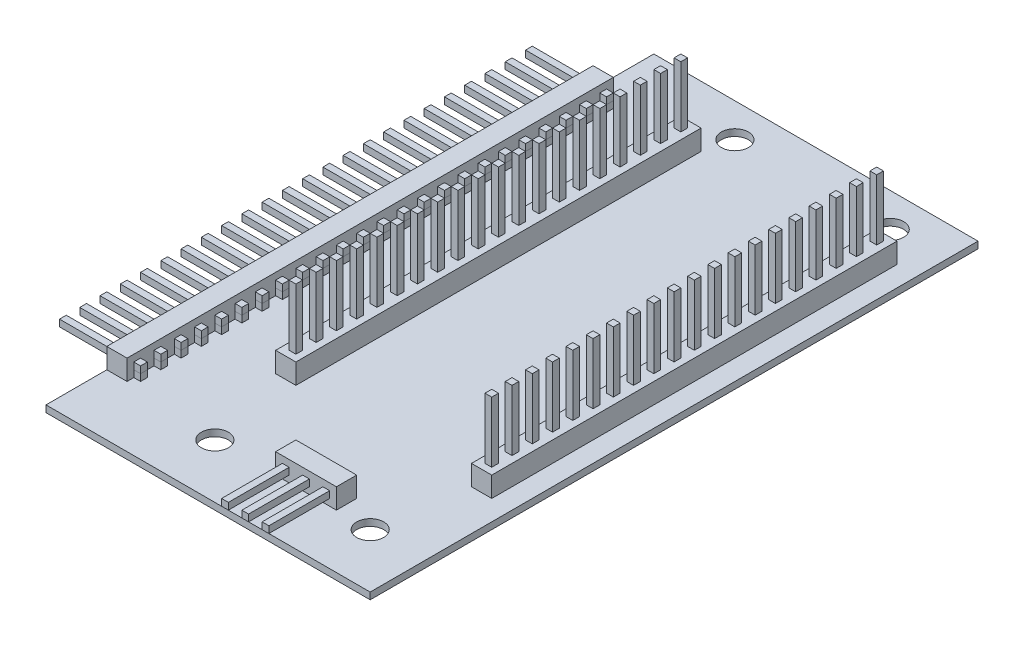
SolidWorks part; units mm, degrees
ref_plane "Front Plane" through (0, 0, 0) normal (0, 0, 1) x (1, 0, 0)
ref_plane "Top Plane" through (0, 0, 0) normal (0, 1, 0) x (1, 0, 0)
ref_plane "Right Plane" through (0, 0, 0) normal (1, 0, 0) x (0, 0, -1)
sketch "Sketch1" plane through (0, 0, 0) normal (0, 1, 0) x (1, 0, 0)
  line L1 (-19.05, 35.7188) -> (19.05, 35.7188)
  line L2 (-19.05, 35.7188) -> (-19.05, -35.7187)
  line L3 (-19.05, -35.7187) -> (19.05, -35.7187)
  line L4 (19.05, 35.7188) -> (19.05, -35.7187)
  line L5 (-19.05, 35.7188) -> (19.05, -35.7187) construction
  line L6 (-19.05, -35.7187) -> (19.05, 35.7188) construction
  point P0 (0, 0)
  dimension "D1" = 38.1
  dimension "D2" = 71.4375
extrude "Boss-Extrude1" add sketch "Sketch1" along normal blind 0.7937
sketch "Sketch2" plane through (0, 0.7937, 0) normal (0, 1, 0) x (1, 0, 0)
  line L0 (0, 0) -> (-19.05, 0) construction
  line L1 (-19.05, 35.7188) -> (-19.05, -35.7187) construction
  line L2 (-19.05, 4.7625) -> (-25.5985, 4.7625) construction
  line L3 (-15.875, 0.7937) -> (-25.4, 0.7937)
  line L4 (-15.875, 0.7937) -> (-15.875, 1.5875)
  line L5 (-15.875, 1.5875) -> (-25.4, 1.5875)
  line L6 (-25.4, 0.7937) -> (-25.4, 1.5875)
  line L7 (-25.4, 3.175) -> (-15.875, 3.175)
  line L8 (-25.4, 3.175) -> (-25.4, 3.9687)
  line L9 (-25.4, 3.9687) -> (-15.875, 3.9687)
  line L10 (-15.875, 3.175) -> (-15.875, 3.9687)
  line L11 (-15.875, 7.9375) -> (-25.4, 7.9375)
  line L12 (-25.4, 8.7312) -> (-25.4, 7.9375)
  line L13 (-15.875, 8.7312) -> (-25.4, 8.7312)
  line L14 (-15.875, 8.7312) -> (-15.875, 7.9375)
  line L15 (-25.4, 5.5562) -> (-15.875, 5.5562)
  line L16 (-15.875, 6.35) -> (-15.875, 5.5562)
  line L17 (-25.4, 6.35) -> (-15.875, 6.35)
  line L18 (-25.4, 6.35) -> (-25.4, 5.5562)
  line L19 (-19.05, 9.525) -> (-25.9028, 9.525) construction
  line L20 (-15.875, 10.3187) -> (-15.875, 11.1125)
  line L21 (-15.875, 10.3187) -> (-25.4, 10.3187)
  line L22 (-25.4, 10.3187) -> (-25.4, 11.1125)
  line L23 (-15.875, 11.1125) -> (-25.4, 11.1125)
  line L24 (-25.4, 12.7) -> (-25.4, 13.4937)
  line L25 (-25.4, 12.7) -> (-15.875, 12.7)
  line L26 (-15.875, 12.7) -> (-15.875, 13.4937)
  line L27 (-25.4, 13.4937) -> (-15.875, 13.4937)
  line L28 (-25.4, 15.0812) -> (-15.875, 15.0812)
  line L29 (-15.875, 15.875) -> (-15.875, 15.0812)
  line L30 (-25.4, 15.875) -> (-15.875, 15.875)
  line L31 (-25.4, 15.875) -> (-25.4, 15.0812)
  line L32 (-15.875, 17.4625) -> (-25.4, 17.4625)
  line L33 (-25.4, 18.2562) -> (-25.4, 17.4625)
  line L34 (-15.875, 18.2562) -> (-25.4, 18.2562)
  line L35 (-15.875, 18.2562) -> (-15.875, 17.4625)
  line L36 (-19.05, 19.05) -> (-25.9028, 19.05) construction
  line L37 (-15.875, 19.8437) -> (-15.875, 20.6375)
  line L38 (-15.875, 19.8437) -> (-25.4, 19.8437)
  line L39 (-25.4, 19.8437) -> (-25.4, 20.6375)
  line L40 (-15.875, 20.6375) -> (-25.4, 20.6375)
  line L41 (-25.4, 22.225) -> (-25.4, 23.0187)
  line L42 (-25.4, 22.225) -> (-15.875, 22.225)
  line L43 (-15.875, 22.225) -> (-15.875, 23.0187)
  line L44 (-25.4, 23.0187) -> (-15.875, 23.0187)
  line L45 (-25.4, 25.4) -> (-15.875, 25.4)
  line L46 (-15.875, 25.4) -> (-15.875, 24.6062)
  line L47 (-25.4, 24.6062) -> (-15.875, 24.6062)
  line L48 (-25.4, 25.4) -> (-25.4, 24.6062)
  line L49 (-15.875, 27.7812) -> (-25.4, 27.7812)
  line L50 (-25.4, 27.7812) -> (-25.4, 26.9875)
  line L51 (-15.875, 26.9875) -> (-25.4, 26.9875)
  line L52 (-15.875, 27.7812) -> (-15.875, 26.9875)
  line L53 (-19.05, -19.05) -> (-25.9028, -19.05) construction
  line L54 (-19.05, -9.525) -> (-25.9028, -9.525) construction
  line L55 (-19.05, -4.7625) -> (-25.5985, -4.7625) construction
  line L56 (-15.875, -27.7812) -> (-15.875, -26.9875)
  line L57 (-15.875, -26.9875) -> (-25.4, -26.9875)
  line L58 (-25.4, -27.7812) -> (-25.4, -26.9875)
  line L59 (-15.875, -27.7812) -> (-25.4, -27.7812)
  line L60 (-25.4, -25.4) -> (-25.4, -24.6062)
  line L61 (-25.4, -24.6062) -> (-15.875, -24.6062)
  line L62 (-15.875, -25.4) -> (-15.875, -24.6062)
  line L63 (-25.4, -25.4) -> (-15.875, -25.4)
  line L64 (-25.4, -23.0187) -> (-15.875, -23.0187)
  line L65 (-15.875, -22.225) -> (-15.875, -23.0187)
  line L66 (-25.4, -22.225) -> (-15.875, -22.225)
  line L67 (-25.4, -22.225) -> (-25.4, -23.0187)
  line L68 (-15.875, -20.6375) -> (-25.4, -20.6375)
  line L69 (-25.4, -19.8437) -> (-25.4, -20.6375)
  line L70 (-15.875, -19.8437) -> (-25.4, -19.8437)
  line L71 (-15.875, -19.8437) -> (-15.875, -20.6375)
  line L72 (-15.875, -18.2562) -> (-15.875, -17.4625)
  line L73 (-15.875, -18.2562) -> (-25.4, -18.2562)
  line L74 (-25.4, -18.2562) -> (-25.4, -17.4625)
  line L75 (-15.875, -17.4625) -> (-25.4, -17.4625)
  line L76 (-25.4, -15.875) -> (-25.4, -15.0812)
  line L77 (-25.4, -15.875) -> (-15.875, -15.875)
  line L78 (-15.875, -15.875) -> (-15.875, -15.0812)
  line L79 (-25.4, -15.0812) -> (-15.875, -15.0812)
  line L80 (-25.4, -13.4937) -> (-15.875, -13.4937)
  line L81 (-15.875, -12.7) -> (-15.875, -13.4937)
  line L82 (-25.4, -12.7) -> (-15.875, -12.7)
  line L83 (-25.4, -12.7) -> (-25.4, -13.4937)
  line L84 (-15.875, -11.1125) -> (-25.4, -11.1125)
  line L85 (-25.4, -10.3187) -> (-25.4, -11.1125)
  line L86 (-15.875, -10.3187) -> (-25.4, -10.3187)
  line L87 (-15.875, -10.3187) -> (-15.875, -11.1125)
  line L88 (-25.4, -6.35) -> (-25.4, -5.5562)
  line L89 (-25.4, -6.35) -> (-15.875, -6.35)
  line L90 (-15.875, -6.35) -> (-15.875, -5.5562)
  line L91 (-25.4, -5.5562) -> (-15.875, -5.5562)
  line L92 (-15.875, -8.7312) -> (-15.875, -7.9375)
  line L93 (-15.875, -8.7312) -> (-25.4, -8.7312)
  line L94 (-25.4, -8.7312) -> (-25.4, -7.9375)
  line L95 (-15.875, -7.9375) -> (-25.4, -7.9375)
  line L96 (-15.875, -3.175) -> (-15.875, -3.9687)
  line L97 (-25.4, -3.9687) -> (-15.875, -3.9687)
  line L98 (-25.4, -3.175) -> (-25.4, -3.9687)
  line L99 (-25.4, -3.175) -> (-15.875, -3.175)
  line L100 (-25.4, -0.7937) -> (-25.4, -1.5875)
  line L101 (-15.875, -1.5875) -> (-25.4, -1.5875)
  line L102 (-15.875, -0.7937) -> (-15.875, -1.5875)
  line L103 (-15.875, -0.7937) -> (-25.4, -0.7937)
  line L104 (-16.6688, 27.7812) -> (-16.6688, 26.9875)
  line L105 (-16.6688, -26.9875) -> (-16.6688, -27.7813)
  line L106 (-16.6688, -24.6062) -> (-16.6688, -25.4)
  line L107 (-16.6688, -22.225) -> (-16.6688, -23.0187)
  line L108 (-16.6688, -17.4625) -> (-16.6688, -20.6375)
  line L109 (-16.6688, -15.0812) -> (-16.6688, -15.875)
  line L110 (-16.6688, -12.7) -> (-16.6688, -13.4937)
  line L111 (-16.6688, -10.3187) -> (-16.6688, -11.1125)
  line L112 (-16.6688, -7.9375) -> (-16.6688, -8.7312)
  line L113 (-16.6688, -5.5562) -> (-16.6688, -6.35)
  line L114 (-16.6688, -3.175) -> (-16.6688, -3.9687)
  line L115 (-16.6688, -0.7937) -> (-16.6688, -1.5875)
  line L116 (-16.6688, 11.1125) -> (-16.6688, 10.3187)
  line L117 (-16.6688, 8.7312) -> (-16.6688, 7.9375)
  line L118 (-16.6688, 6.35) -> (-16.6688, 5.5562)
  line L119 (-16.6688, 3.9687) -> (-16.6688, 3.175)
  line L120 (-16.6688, 1.5875) -> (-16.6688, 0.7938)
  line L121 (-16.6688, 13.4937) -> (-16.6688, 12.7)
  line L122 (-16.6688, 15.875) -> (-16.6688, 15.0812)
  line L123 (-16.6688, 18.2562) -> (-16.6688, 17.4625)
  line L124 (-16.6688, 20.6375) -> (-16.6688, 19.8437)
  line L125 (-16.6688, 23.0187) -> (-16.6688, 22.225)
  line L126 (-16.6688, 25.4) -> (-16.6688, 24.6062)
  point P9 (-25.4, 1.1906)
  dimension "D1" = 3.175
  dimension "D2" = 6.35
  dimension "D3" = 0.7937
  dimension "D4" = 0.7937
  dimension "D5" = 1.5875
  dimension "D6" = 0.7937
  dimension "D7" = 0.7937
  dimension "D8" = 0.7937
  dimension "D9" = 0.7937
extrude "Boss-Extrude2" add sketch "Sketch2" along normal blind 0.7937 separate body contours L49 L104 L51 L52 | L45 L126 L47 L46 | L44 L125 L42 L43 | L40 L124 L38 L37 | L34 L123 L32 L35 | L30 L122 L28 L29 | L27 L121 L25 L26 | L23 L116 L21 L20 | L13 L117 L11 L14 | L17 L118 L15 L16 | L9 L119 L7 L10 | L5 L120 L3 L4 | L103 L115 L101 L102 | L99 L114 L97 L96 | L91 L113 L89 L90 | L95 L112 L93 L92 | L86 L111 L84 L87 | L82 L110 L80 L81 | L79 L109 L77 L78 | L75 L108 L73 L72 | L70 L108 L68 L71 | L66 L107 L64 L65 | L61 L106 L63 L62 | L57 L105 L59 L56 region at (-16.2719, 0.7937, -1.1906) region at (-16.2719, 0.7937, -3.5719) region at (-16.2719, 0.7937, -8.3344) region at (-16.2719, 0.7937, -5.9531) region at (-16.2719, 0.7937, -10.7156) region at (-16.2719, 0.7937, -13.0969) region at (-16.2719, 0.7937, -15.4781) region at (-16.2719, 0.7937, -17.8594) region at (-16.2719, 0.7937, -20.2406) region at (-16.2719, 0.7937, -22.6219) region at (-16.2719, 0.7937, -25.0031) region at (-16.2719, 0.7937, -27.3844) region at (-16.2719, 0.7937, 27.3844) region at (-16.2719, 0.7937, 25.0031) region at (-16.2719, 0.7937, 22.6219) region at (-16.2719, 0.7937, 17.8594) region at (-16.2719, 0.7937, 20.2406) region at (-16.2719, 0.7937, 15.4781) region at (-16.2719, 0.7937, 13.0969) region at (-16.2719, 0.7937, 10.7156) region at (-16.2719, 0.7937, 5.9531) region at (-16.2719, 0.7937, 8.3344) region at (-16.2719, 0.7937, 3.5719) region at (-16.2719, 0.7937, 1.1906)
extrude "Boss-Extrude3" add sketch "Sketch2<3>" along normal blind 0.7937 from offset 0.7937 contours L51 L50 L49 L52 | L45 L46 L47 L48 | L44 L43 L42 L41 | L40 L39 L38 L37 | L34 L33 L32 L35 | L30 L29 L28 L31 | L27 L26 L25 L24 | L23 L22 L21 L20 | L13 L12 L11 L14 | L17 L16 L15 L18 | L9 L10 L7 L8 | L5 L6 L3 L4 | L103 L100 L101 L102 | L99 L96 L97 L98 | L91 L90 L89 L88 | L95 L94 L93 L92 | L86 L85 L84 L87 | L82 L81 L80 L83 | L79 L78 L77 L76 | L75 L74 L73 L72 | L70 L69 L68 L71 | L66 L65 L64 L67 | L61 L62 L63 L60 | L57 L58 L59 L56
sketch "Sketch2<3>" plane through (0, 0.7937, 0) normal (0, 1, 0) x (1, 0, 0) same geometry as "Sketch2"
sketch "Sketch3" plane through (0, 0.7937, 0) normal (0, 1, 0) x (1, 0, 0)
  line L0 (-19.05, 35.7188) -> (-19.05, -35.7187) construction
  line L1 (-19.05, 28.575) -> (-16.6688, 28.575)
  line L2 (-19.05, 28.575) -> (-19.05, -28.575)
  line L3 (-19.05, -28.575) -> (-16.6687, -28.575)
  line L4 (-16.6688, 28.575) -> (-16.6687, -28.575)
  line L5 (-15.875, 27.7812) -> (-25.4, 27.7812) construction
  line L6 (-15.875, -27.7812) -> (-25.4, -27.7812) construction
  dimension "D1" = 2.3813
  dimension "D2" = 0.7937
  dimension "D3" = 0.7937
extrude "Boss-Extrude4" add sketch "Sketch3" along normal blind 2.3813 separate body
sketch "Sketch4" plane through (0, 0.7937, 0) normal (0, 1, 0) x (1, 0, 0)
  line L0 (19.05, 4.7625) -> (-19.05, 4.7625) construction
  line L1 (-15.875, 27.7812) -> (-25.4, 27.7812) construction
  line L2 (19.05, -35.7187) -> (19.05, 35.7188) construction
  line L4 (-7.9375, 25.4) -> (-7.1438, 25.4)
  line L5 (-7.9375, 25.4) -> (-7.9375, 24.6062)
  line L6 (-7.9375, 24.6062) -> (-7.1438, 24.6062)
  line L7 (-7.1438, 25.4) -> (-7.1438, 24.6062)
  line L8 (-7.9375, 23.0187) -> (-7.1438, 23.0187)
  line L9 (-7.9375, 23.0187) -> (-7.9375, 22.225)
  line L10 (-7.9375, 22.225) -> (-7.1438, 22.225)
  line L11 (-7.1438, 23.0187) -> (-7.1438, 22.225)
  line L12 (-7.9375, 20.6375) -> (-7.1438, 20.6375)
  line L13 (-7.9375, 20.6375) -> (-7.9375, 19.8437)
  line L14 (-7.9375, 19.8437) -> (-7.1438, 19.8437)
  line L15 (-7.1438, 20.6375) -> (-7.1438, 19.8437)
  line L16 (-7.9375, 18.2562) -> (-7.1438, 18.2562)
  line L17 (-7.9375, 18.2562) -> (-7.9375, 17.4625)
  line L18 (-7.9375, 17.4625) -> (-7.1438, 17.4625)
  line L19 (-7.1438, 18.2562) -> (-7.1438, 17.4625)
  line L20 (-7.9375, 15.875) -> (-7.1438, 15.875)
  line L21 (-7.9375, 15.875) -> (-7.9375, 15.0813)
  line L22 (-7.9375, 15.0813) -> (-7.1438, 15.0813)
  line L23 (-7.1438, 15.875) -> (-7.1438, 15.0813)
  line L24 (-7.9375, 13.4938) -> (-7.1438, 13.4937)
  line L25 (-7.9375, 13.4938) -> (-7.9375, 12.7)
  line L26 (-7.9375, 12.7) -> (-7.1438, 12.7)
  line L27 (-7.1438, 13.4937) -> (-7.1438, 12.7)
  line L28 (-7.9375, 11.1125) -> (-7.1438, 11.1125)
  line L29 (-7.9375, 11.1125) -> (-7.9375, 10.3187)
  line L30 (-7.9375, 10.3187) -> (-7.1438, 10.3187)
  line L31 (-7.1438, 11.1125) -> (-7.1438, 10.3187)
  line L32 (-7.9375, 8.7312) -> (-7.1438, 8.7312)
  line L33 (-7.9375, 8.7312) -> (-7.9375, 7.9375)
  line L34 (-7.9375, 7.9375) -> (-7.1438, 7.9375)
  line L35 (-7.1438, 8.7312) -> (-7.1438, 7.9375)
  line L36 (-7.9375, 27.7812) -> (-7.1438, 27.7812)
  line L37 (-7.9375, 27.7812) -> (-7.9375, 26.9875)
  line L38 (-7.9375, 26.9875) -> (-7.1438, 26.9875)
  line L39 (-7.1438, 27.7812) -> (-7.1438, 26.9875)
  line L40 (-7.9375, 6.35) -> (-7.1438, 6.35)
  line L41 (-7.9375, 6.35) -> (-7.9375, 5.5562)
  line L42 (-7.9375, 5.5562) -> (-7.1438, 5.5562)
  line L43 (-7.1438, 6.35) -> (-7.1438, 5.5562)
  line L44 (-19.05, 28.575) -> (-19.05, -28.575) construction
  line L45 (-7.1438, 3.175) -> (-7.1438, 3.9687)
  line L46 (-7.9375, 3.9687) -> (-7.1438, 3.9687)
  line L47 (-7.9375, 3.175) -> (-7.9375, 3.9687)
  line L48 (-7.9375, 3.175) -> (-7.1438, 3.175)
  line L49 (-7.1438, -18.2562) -> (-7.1438, -17.4625)
  line L50 (-7.9375, -17.4625) -> (-7.1438, -17.4625)
  line L51 (-7.9375, -18.2562) -> (-7.9375, -17.4625)
  line L52 (-7.9375, -18.2562) -> (-7.1438, -18.2562)
  line L53 (-7.1438, 0.7937) -> (-7.1438, 1.5875)
  line L54 (-7.9375, 1.5875) -> (-7.1438, 1.5875)
  line L55 (-7.9375, 0.7937) -> (-7.9375, 1.5875)
  line L56 (-7.9375, 0.7937) -> (-7.1438, 0.7937)
  line L57 (-7.1438, -1.5875) -> (-7.1438, -0.7938)
  line L58 (-7.9375, -0.7938) -> (-7.1438, -0.7938)
  line L59 (-7.9375, -1.5875) -> (-7.9375, -0.7938)
  line L60 (-7.9375, -1.5875) -> (-7.1438, -1.5875)
  line L61 (-7.1438, -3.9688) -> (-7.1438, -3.175)
  line L62 (-7.9375, -3.175) -> (-7.1438, -3.175)
  line L63 (-7.9375, -3.9688) -> (-7.9375, -3.175)
  line L64 (-7.9375, -3.9688) -> (-7.1438, -3.9688)
  line L65 (-7.1438, -6.35) -> (-7.1438, -5.5563)
  line L66 (-7.9375, -5.5563) -> (-7.1438, -5.5563)
  line L67 (-7.9375, -6.35) -> (-7.9375, -5.5563)
  line L68 (-7.9375, -6.35) -> (-7.1438, -6.35)
  line L69 (-7.1438, -8.7313) -> (-7.1438, -7.9375)
  line L70 (-7.9375, -7.9375) -> (-7.1438, -7.9375)
  line L71 (-7.9375, -8.7313) -> (-7.9375, -7.9375)
  line L72 (-7.9375, -8.7313) -> (-7.1438, -8.7313)
  line L73 (-7.1438, -11.1125) -> (-7.1438, -10.3188)
  line L74 (-7.9375, -10.3188) -> (-7.1438, -10.3188)
  line L75 (-7.9375, -11.1125) -> (-7.9375, -10.3188)
  line L76 (-7.9375, -11.1125) -> (-7.1438, -11.1125)
  line L77 (-7.1438, -13.4937) -> (-7.1438, -12.7)
  line L78 (-7.9375, -12.7) -> (-7.1438, -12.7)
  line L79 (-7.9375, -13.4937) -> (-7.9375, -12.7)
  line L80 (-7.9375, -13.4937) -> (-7.1438, -13.4937)
  line L81 (-7.1438, -15.875) -> (-7.1438, -15.0812)
  line L82 (-7.9375, -15.0812) -> (-7.1438, -15.0812)
  line L83 (-7.9375, -15.875) -> (-7.9375, -15.0812)
  line L84 (-7.9375, -15.875) -> (-7.1438, -15.875)
  line L85 (3.9688, 35.7188) -> (3.9688, -35.7187) construction
  line L86 (19.05, 35.7188) -> (-19.05, 35.7188) construction
  line L87 (-19.05, -35.7187) -> (19.05, -35.7187) construction
  line L88 (15.875, -15.875) -> (15.0813, -15.875)
  line L89 (15.875, -15.875) -> (15.875, -15.0812)
  line L90 (15.875, -15.0812) -> (15.0813, -15.0812)
  line L91 (15.0813, -15.875) -> (15.0813, -15.0812)
  line L92 (15.875, -13.4937) -> (15.0813, -13.4937)
  line L93 (15.875, -13.4937) -> (15.875, -12.7)
  line L94 (15.875, -12.7) -> (15.0813, -12.7)
  line L95 (15.0813, -13.4937) -> (15.0813, -12.7)
  line L96 (15.875, -11.1125) -> (15.0813, -11.1125)
  line L97 (15.875, -11.1125) -> (15.875, -10.3188)
  line L98 (15.875, -10.3188) -> (15.0813, -10.3188)
  line L99 (15.0813, -11.1125) -> (15.0813, -10.3188)
  line L100 (15.875, -8.7313) -> (15.0813, -8.7313)
  line L101 (15.875, -8.7313) -> (15.875, -7.9375)
  line L102 (15.875, -7.9375) -> (15.0813, -7.9375)
  line L103 (15.0813, -8.7313) -> (15.0813, -7.9375)
  line L104 (15.875, -6.35) -> (15.0813, -6.35)
  line L105 (15.875, -6.35) -> (15.875, -5.5563)
  line L106 (15.875, -5.5563) -> (15.0813, -5.5563)
  line L107 (15.0813, -6.35) -> (15.0813, -5.5563)
  line L108 (15.875, -3.9688) -> (15.0813, -3.9688)
  line L109 (15.875, -3.9688) -> (15.875, -3.175)
  line L110 (15.875, -3.175) -> (15.0813, -3.175)
  line L111 (15.0813, -3.9688) -> (15.0813, -3.175)
  line L112 (15.875, -1.5875) -> (15.0813, -1.5875)
  line L113 (15.875, -1.5875) -> (15.875, -0.7938)
  line L114 (15.875, -0.7938) -> (15.0813, -0.7938)
  line L115 (15.0813, -1.5875) -> (15.0813, -0.7938)
  line L116 (15.875, 0.7937) -> (15.0813, 0.7937)
  line L117 (15.875, 0.7937) -> (15.875, 1.5875)
  line L118 (15.875, 1.5875) -> (15.0813, 1.5875)
  line L119 (15.0813, 0.7937) -> (15.0813, 1.5875)
  line L120 (15.875, -18.2562) -> (15.0813, -18.2562)
  line L121 (15.875, -18.2562) -> (15.875, -17.4625)
  line L122 (15.875, -17.4625) -> (15.0813, -17.4625)
  line L123 (15.0813, -18.2562) -> (15.0813, -17.4625)
  line L124 (15.875, 3.175) -> (15.0813, 3.175)
  line L125 (15.875, 3.175) -> (15.875, 3.9687)
  line L126 (15.875, 3.9687) -> (15.0813, 3.9687)
  line L127 (15.0813, 3.175) -> (15.0813, 3.9687)
  line L128 (15.0813, 6.35) -> (15.0813, 5.5562)
  line L129 (15.875, 5.5563) -> (15.0813, 5.5562)
  line L130 (15.875, 6.35) -> (15.875, 5.5563)
  line L131 (15.875, 6.35) -> (15.0813, 6.35)
  line L132 (15.0813, 27.7812) -> (15.0813, 26.9875)
  line L133 (15.875, 26.9875) -> (15.0813, 26.9875)
  line L134 (15.875, 27.7812) -> (15.875, 26.9875)
  line L135 (15.875, 27.7812) -> (15.0813, 27.7812)
  line L136 (15.0813, 8.7312) -> (15.0813, 7.9375)
  line L137 (15.875, 7.9375) -> (15.0813, 7.9375)
  line L138 (15.875, 8.7313) -> (15.875, 7.9375)
  line L139 (15.875, 8.7313) -> (15.0813, 8.7312)
  line L140 (15.0813, 11.1125) -> (15.0813, 10.3187)
  line L141 (15.875, 10.3188) -> (15.0813, 10.3187)
  line L142 (15.875, 11.1125) -> (15.875, 10.3188)
  line L143 (15.875, 11.1125) -> (15.0813, 11.1125)
  line L144 (15.0813, 13.4937) -> (15.0813, 12.7)
  line L145 (15.875, 12.7) -> (15.0813, 12.7)
  line L146 (15.875, 13.4938) -> (15.875, 12.7)
  line L147 (15.875, 13.4938) -> (15.0813, 13.4937)
  line L148 (15.0813, 15.875) -> (15.0813, 15.0813)
  line L149 (15.875, 15.0813) -> (15.0813, 15.0813)
  line L150 (15.875, 15.875) -> (15.875, 15.0813)
  line L151 (15.875, 15.875) -> (15.0813, 15.875)
  line L152 (15.0813, 18.2562) -> (15.0813, 17.4625)
  line L153 (15.875, 17.4625) -> (15.0813, 17.4625)
  line L154 (15.875, 18.2563) -> (15.875, 17.4625)
  line L155 (15.875, 18.2563) -> (15.0813, 18.2562)
  line L156 (15.0813, 20.6375) -> (15.0813, 19.8437)
  line L157 (15.875, 19.8438) -> (15.0813, 19.8437)
  line L158 (15.875, 20.6375) -> (15.875, 19.8438)
  line L159 (15.875, 20.6375) -> (15.0813, 20.6375)
  line L160 (15.0813, 23.0187) -> (15.0813, 22.225)
  line L161 (15.875, 22.225) -> (15.0813, 22.225)
  line L162 (15.875, 23.0187) -> (15.875, 22.225)
  line L163 (15.875, 23.0187) -> (15.0813, 23.0187)
  line L164 (15.0813, 25.4) -> (15.0813, 24.6062)
  line L165 (15.875, 24.6062) -> (15.0813, 24.6062)
  line L166 (15.875, 25.4) -> (15.875, 24.6062)
  line L167 (15.875, 25.4) -> (15.0813, 25.4)
  dimension "D2" = 1.5875
  dimension "D3" = 1.5875
  dimension "D4" = 1.5875
  dimension "D5" = 1.5875
  dimension "D6" = 1.5875
  dimension "D7" = 1.5875
  dimension "D8" = 1.5875
  dimension "D9" = 1.5875
  dimension "D10" = 1.5875
  dimension "D11" = 26.1937
  dimension "D12" = 0.7937
  dimension "D13" = 0.7937
  dimension "D14" = 11.1125
extrude "Boss-Extrude5" add sketch "Sketch4" along normal blind 9.525 separate body
sketch "Sketch5" plane through (0, 0.7937, 0) normal (0, 1, 0) x (1, 0, 0)
  line L1 (-8.7313, 28.575) -> (-6.35, 28.575)
  line L2 (-8.7313, 28.575) -> (-8.7313, -19.05)
  line L3 (-8.7313, -19.05) -> (-6.35, -19.05)
  line L4 (-6.35, 28.575) -> (-6.35, -19.05)
  line L5 (14.2875, 28.575) -> (16.6688, 28.575)
  line L6 (14.2875, 28.575) -> (14.2875, -19.05)
  line L7 (14.2875, -19.05) -> (16.6688, -19.05)
  line L8 (16.6688, 28.575) -> (16.6688, -19.05)
  line L11 (-7.9375, -18.2562) -> (-7.1438, -18.2562) construction
  line L12 (-7.1438, 27.7812) -> (-7.9375, 27.7812) construction
  line L14 (-19.05, 35.7188) -> (-19.05, -35.7187) construction
  line L15 (19.05, -35.7187) -> (19.05, 35.7188) construction
  dimension "D1" = 2.3813
  dimension "D2" = 0.7937
  dimension "D3" = 0.7937
  dimension "D4" = 2.3813
  dimension "D5" = 10.3187
  dimension "D6" = 4.7625
extrude "Boss-Extrude6" add sketch "Sketch5" along normal blind 2.3813
sketch "Sketch6" plane through (0, 0.7937, 0) normal (0, 1, 0) x (1, 0, 0)
  line L0 (-19.05, -35.7187) -> (19.05, -35.7187) construction
  line L1 (2.3813, -26.1937) -> (3.175, -26.1937)
  line L2 (2.3813, -26.1937) -> (2.3813, -36.5125)
  line L3 (2.3813, -36.5125) -> (3.175, -36.5125)
  line L4 (3.175, -26.1937) -> (3.175, -36.5125)
  line L5 (4.7625, -26.1937) -> (5.5563, -26.1937)
  line L6 (4.7625, -26.1937) -> (4.7625, -36.5125)
  line L7 (4.7625, -36.5125) -> (5.5563, -36.5125)
  line L8 (5.5563, -26.1937) -> (5.5563, -36.5125)
  line L9 (7.1438, -26.1937) -> (7.9375, -26.1937)
  line L10 (7.1438, -26.1937) -> (7.1438, -36.5125)
  line L11 (7.1438, -36.5125) -> (7.9375, -36.5125)
  line L12 (7.9375, -26.1937) -> (7.9375, -36.5125)
  line L13 (2.3813, -26.9875) -> (3.175, -26.9875)
  line L14 (4.7625, -26.9875) -> (5.5563, -26.9875)
  line L15 (7.1438, -26.9875) -> (7.9375, -26.9875)
  line L16 (19.05, -35.7187) -> (19.05, 35.7188) construction
  dimension "D1" = 1.5875
  dimension "D2" = 1.5875
  dimension "D3" = 10.3187
  dimension "D4" = 9.525
  dimension "D5" = 0.7937
  dimension "D6" = 11.1125
  dimension "D7" = 0.7937
extrude "Boss-Extrude7" add sketch "Sketch6" along normal blind 0.7937 contours L2 L13 L4 L1 | L6 L14 L8 L5 | L10 L15 L12 L9 region at (2.7781, 0.7937, 26.5906) region at (5.1594, 0.7937, 26.5906) region at (7.5406, 0.7937, 26.5906)
extrude "Boss-Extrude8" add sketch "Sketch6<3>" along normal blind 0.7937 from offset 0.7937 separate body contours L2 L3 L4 L1 | L6 L7 L8 L5 | L10 L11 L12 L9
sketch "Sketch6<3>" plane through (0, 0.7937, 0) normal (0, 1, 0) x (1, 0, 0) same geometry as "Sketch6"
sketch "Sketch7" plane through (0, 0.7937, 0) normal (0, 1, 0) x (1, 0, 0)
  line L0 (4.7625, -26.1937) -> (5.5563, -26.1937) construction
  line L1 (1.5875, -26.9875) -> (8.7313, -26.9875)
  line L2 (1.5875, -26.9875) -> (1.5875, -29.3687)
  line L3 (1.5875, -29.3687) -> (8.7313, -29.3687)
  line L4 (8.7313, -26.9875) -> (8.7313, -29.3687)
  line L5 (2.3813, -26.1937) -> (2.3813, -36.5125) construction
  line L6 (7.9375, -26.1937) -> (7.9375, -36.5125) construction
  dimension "D1" = 0.7937
  dimension "D2" = 2.3813
  dimension "D3" = 0.7937
  dimension "D4" = 0.7937
extrude "Boss-Extrude9" add sketch "Sketch7" along normal blind 2.3813
sketch "Sketch8" plane through (0, 0.7937, 0) normal (0, 1, 0) x (1, 0, 0)
  line L0 (19.05, 35.7188) -> (-19.05, 35.7188) construction
  line L1 (-5.5563, 31.75) -> (12.7, 31.75) construction
  line L2 (-5.5563, 31.75) -> (-5.5562, -29.3687) construction
  line L3 (-5.5562, -29.3687) -> (12.7, -29.3687) construction
  line L4 (12.7, 31.75) -> (12.7, -29.3687) construction
  line L5 (-5.5563, 31.75) -> (12.7, -29.3687) construction
  line L6 (-5.5562, -29.3687) -> (12.7, 31.75) construction
  line L7 (-19.05, -35.7187) -> (19.05, -35.7187) construction
  line L8 (19.05, -35.7187) -> (19.05, 35.7188) construction
  line L9 (-19.05, 35.7188) -> (-19.05, -35.7187) construction
  circle A0 centre (-5.5563, 31.75) radius 1.5875
  circle A1 centre (12.7, 31.75) radius 1.5875
  circle A2 centre (-5.5562, -29.3687) radius 1.5875
  circle A3 centre (12.7, -29.3687) radius 1.5875
  point P0 (3.5719, 1.1906)
  dimension "D5" = 3.175
  dimension "D1" = 3.9688
  dimension "D2" = 6.35
  dimension "D3" = 6.35
  dimension "D4" = 13.4937
extrude "Cut-Extrude1" cut sketch "Sketch8" against normal through all
